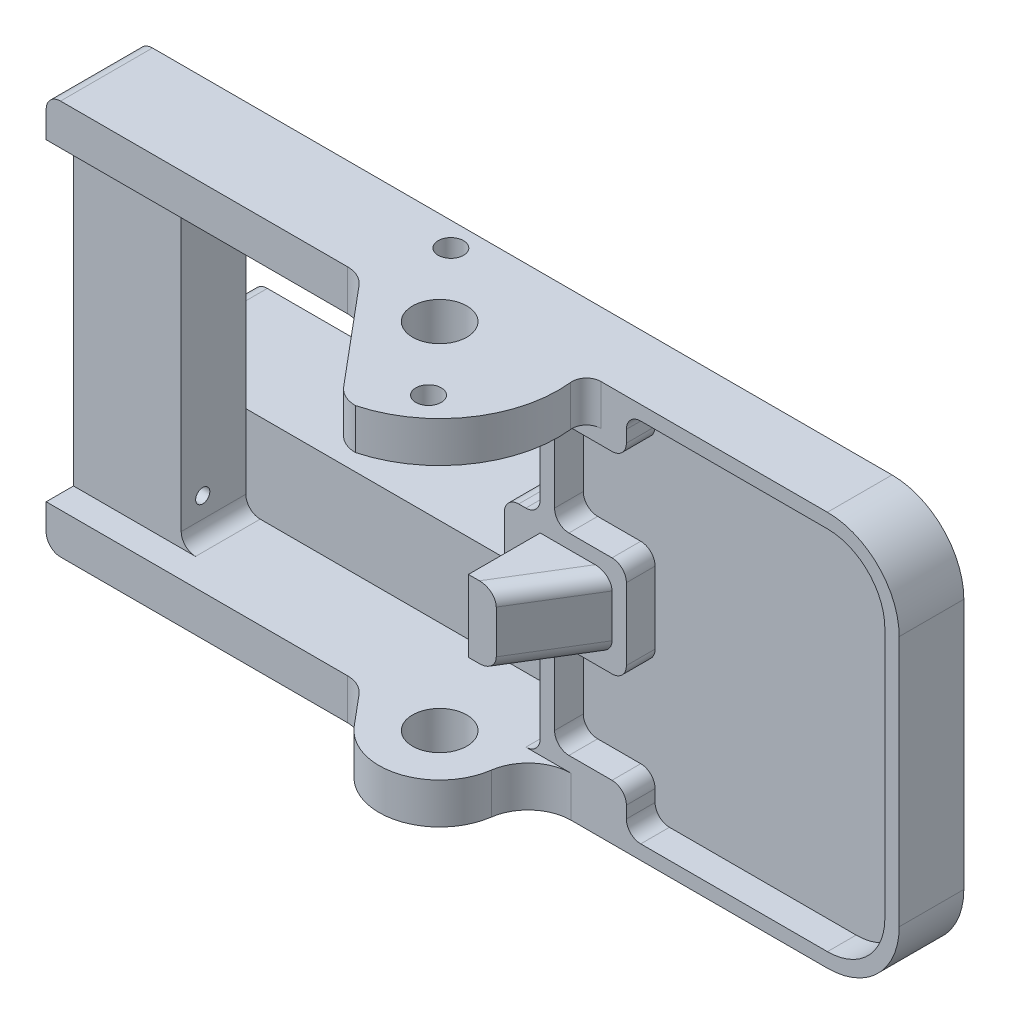
SolidWorks part; units mm, degrees
ref_plane "Front Plane" through (0, 0, 0) normal (0, 0, 1) x (1, 0, 0)
ref_plane "Top Plane" through (0, 0, 0) normal (0, 1, 0) x (1, 0, 0)
ref_plane "Right Plane" through (0, 0, 0) normal (1, 0, 0) x (0, 0, -1)
sketch "Sketch1" plane through (0, 0, 0) normal (0, 0, 1) x (1, 0, 0)
  line L1 (57.15, -34.925) -> (-57.15, -34.925)
  line L2 (57.15, -34.925) -> (57.15, 34.925)
  line L3 (57.15, 34.925) -> (-57.15, 34.925)
  line L4 (-57.15, -34.925) -> (-57.15, 34.925)
  line L5 (57.15, -34.925) -> (-57.15, 34.925) construction
  line L6 (57.15, 34.925) -> (-57.15, -34.925) construction
  point P0 (0, 0)
  dimension "D1" = 69.85
  dimension "D2" = 114.3
extrude "Boss-Extrude1" add sketch "Sketch1" along normal blind 57.15
sketch "Sketch2" plane through (0, 0, 57.15) normal (0, 0, 1) x (1, 0, 0)
  line L0 (-57.15, 34.925) -> (-57.15, -34.925) construction
  line L1 (57.15, -27.725) -> (-57.15, -27.725)
  line L2 (57.15, -27.725) -> (57.15, 27.725)
  line L3 (57.15, 27.725) -> (-57.15, 27.725)
  line L4 (-57.15, -27.725) -> (-57.15, 27.725)
  line L5 (57.15, -27.725) -> (-57.15, 27.725) construction
  line L6 (57.15, 27.725) -> (-57.15, -27.725) construction
  line L7 (57.15, 34.925) -> (-57.15, 34.925) construction
  point P0 (0, 0)
  dimension "D1" = 7.2
extrude "Cut-Extrude2" cut sketch "Sketch2" against normal blind 25.4
sketch "Sketch3" plane through (0, 0, 0) normal (0, 0, -1) x (-1, 0, 0)
  line L0 (-57.15, -34.925) -> (-57.15, 34.925) construction
  line L1 (57.15, 34.925) -> (-57.15, 34.925)
  line L2 (57.15, 34.925) -> (57.15, -12.065)
  line L3 (57.15, -12.065) -> (-57.15, -12.065)
  line L4 (-57.15, 34.925) -> (-57.15, -12.065)
  dimension "D1" = 46.99
extrude "Cut-Extrude3" cut sketch "Sketch3" against normal blind 20.32
sketch "Sketch5" plane through (0, -34.925, 0) normal (0, -1, 0) x (1, 0, 0)
  line L0 (-3.81, 10.79) -> (46.99, 10.79) construction
  line L1 (57.15, 20.32) -> (-57.15, 20.32) construction
  line L2 (57.15, 57.15) -> (57.15, 0) construction
  circle A0 centre (-3.81, 10.79) radius 2.415
  circle A1 centre (46.99, 10.79) radius 2.415
  dimension "D3" = 4.83
  dimension "D4" = 10.16
  dimension "D1" = 9.53
  dimension "D2" = 50.8
extrude "Cut-Extrude4" cut sketch "Sketch5" against normal blind 25.4
sketch "Sketch6" plane through (0, 0, 20.32) normal (0, 0, -1) x (-1, 0, 0)
  line L0 (-49.405, -12.065) -> (6.225, -12.065) construction
  line L1 (-49.405, -12.065) -> (-49.405, -34.925) construction
  line L2 (6.225, -34.925) -> (6.225, -12.065) construction
  line L3 (-57.15, -12.065) -> (57.15, -12.065) construction
  circle A1 centre (-5.08, -1.524) radius 2.2225
  dimension "D3" = 4.445
extrude "Cut-Extrude5" cut sketch "Sketch6" against normal blind 5.08
sketch "Sketch7" plane through (0, -34.925, 0) normal (0, -1, 0) x (1, 0, 0)
  line L0 (57.15, 57.15) -> (57.15, 0) construction
  line L2 (-57.15, 31.75) -> (57.15, 31.75) construction
  circle A0 centre (31.75, 36.83) radius 4.8
  dimension "D1" = 9.6
  dimension "D2" = 25.4
  dimension "D3" = 5.08
extrude "Cut-Extrude6" cut sketch "Sketch7" against normal up to surface (69.85 mm away) up to face at (0, 34.925, 38.735)
sketch "Sketch8" plane through (0, 34.925, 0) normal (0, 1, 0) x (1, 0, 0)
  line L0 (21.4654, -24.5733) -> (42.0346, -49.0867) construction
  line L1 (57.15, -31.75) -> (-57.15, -31.75) construction
  circle A0 centre (31.75, -36.83) radius 16 construction
  circle A1 centre (21.4654, -24.5733) radius 2.25
  circle A2 centre (42.0346, -49.0867) radius 2.25
  dimension "D1" = 32
  dimension "D2" = 4.5
  dimension "D3" = 50
sketch "Sketch9" plane through (0, 0, 31.75) normal (0, 0, 1) x (1, 0, 0)
  line L0 (57.15, 34.925) -> (-57.15, 34.925) construction
  line L5 (57.15, 27.725) -> (-57.15, 27.725) construction
  line L6 (-19.05, 27.725) -> (44.45, 27.725)
  line L7 (-19.05, 27.725) -> (-19.05, -27.725)
  line L8 (-19.05, -27.725) -> (44.45, -27.725)
  line L9 (44.45, 27.725) -> (44.45, -27.725)
  line L10 (-57.15, -27.725) -> (57.15, -27.725) construction
  line L11 (-57.15, 27.725) -> (-57.15, -27.725) construction
  line L12 (57.15, -27.725) -> (57.15, 27.725) construction
  line L13 (-57.15, -34.925) -> (-38.1, -34.925)
  line L14 (-57.15, -34.925) -> (-57.15, 34.925)
  line L15 (-57.15, 34.925) -> (-38.1, 34.925)
  line L16 (-38.1, -34.925) -> (-38.1, 34.925)
  line L17 (-57.15, -34.925) -> (-38.1, 34.925) construction
  line L18 (-57.15, 34.925) -> (-38.1, -34.925) construction
  line L19 (-57.15, -34.925) -> (57.15, -34.925) construction
  point P5 (-47.625, 0)
  dimension "D1" = 12.7
  dimension "25in" = 38.1
  dimension "D2" = 19.05
extrude "Cut-Extrude7" cut sketch "Sketch9" against normal through all both and the other way through all
extrude "Cut-Extrude8" cut sketch "Sketch8" against normal up to next
sketch "Sketch10" [suppressed] plane through (0, 0, 29.21) normal (0, 0, 1) x (1, 0, 0)
  line L1 (-30.607, -1.778) -> (-30.607, -6.604) construction
  circle A0 centre (-33.2489, -4.191) radius 2.286
  point P5 (-30.607, -4.191)
  dimension "D1" = 4.572
sketch "Sketch11" [suppressed] plane through (0, 0, 21.59) normal (0, 0, -1) x (-1, 0, 0)
  circle A0 centre (33.2489, -4.191) radius 2.286
  dimension "D1" = 4.572
extrude "Cut-Extrude9" [suppressed] cut sketch "Sketch11" against normal blind 3.81
sketch "Sketch12" plane through (-19.05, 0, 0) normal (1, 0, 0) x (0, 0, -1)
  line L0 (-31.75, -27.725) -> (-31.75, 27.725) construction
  line L1 (-27.94, -21.59) -> (-27.94, 21.59) construction
  line L2 (-20.32, 27.725) -> (-20.32, -12.065) construction
  circle A0 centre (-27.94, -21.59) radius 1.25
  circle A1 centre (-27.94, 21.59) radius 1.25
  point P0 (-31.75, 0)
  point P8 (-27.94, 0)
  dimension "D1" = 2.5
  dimension "D2" = 7.62
  dimension "D3" = 43.18
extrude "Cut-Extrude10" cut sketch "Sketch12" against normal up to surface (19.05 mm away) up to face at (-38.1, -2.413, 33.274)
sketch "Sketch13" plane through (0, 34.925, 0) normal (0, 1, 0) x (1, 0, 0)
  line L0 (-38.1, -36.5854) -> (17.5354, -36.5854)
  line L1 (17.5354, -36.5854) -> (34.7911, -57.15)
  line L2 (57.15, -57.15) -> (-38.1, -57.15) construction
  line L3 (42.0346, -49.0867) -> (21.4654, -24.5733) construction
  line L4 (-38.1, -36.5854) -> (-38.1, -57.15)
  line L5 (-38.1, -57.15) -> (34.7911, -57.15)
  line L6 (-38.1, -20.32) -> (-38.1, -57.15) construction
extrude "Cut-Extrude12" cut sketch "Sketch13" against normal through all
sketch "Sketch14" plane through (44.45, 0, 0) normal (-1, 0, 0) x (0, 0, 1)
  line L0 (0, -27.725) -> (31.75, -27.725) construction
  line L1 (20.32, -12.065) -> (0, -12.065)
  line L2 (20.32, -12.065) -> (20.32, -27.725)
  line L3 (20.32, -27.725) -> (0, -27.725)
  line L4 (0, -12.065) -> (0, -27.725)
extrude "Boss-Extrude2" add sketch "Sketch14" along normal up to next
sketch "Sketch15" plane through (0, 0, 20.32) normal (0, 0, -1) x (-1, 0, 0)
  line L0 (22.6367, 0.762) -> (22.6367, -4.064) construction
  line L2 (17.6714, 0.8658) -> (32.5377, 0.555) construction
  line L3 (22.6367, 0.762) -> (22.6367, -4.064) construction
  line L4 (27.4632, -4.064) -> (17.5572, -4.064) construction
  line L5 (21.717, -0.889) -> (21.717, 3.937) construction
  circle A0 centre (23.967, -1.651) radius 2.25
  point P4 (22.6367, -1.651)
  dimension "D1" = 4.5
extrude "Cut-Extrude13" cut sketch "Sketch15" against normal blind 5.08
sketch "Sketch16" plane through (0, 0, 31.75) normal (0, 0, 1) x (1, 0, 0)
  line L0 (44.45, -27.725) -> (44.45, 27.725) construction
  line L1 (57.15, -6.35) -> (44.45, -6.35)
  line L2 (57.15, -6.35) -> (57.15, 6.35)
  line L3 (57.15, 6.35) -> (44.45, 6.35)
  line L4 (44.45, -6.35) -> (44.45, 6.35)
  line L5 (57.15, -6.35) -> (44.45, 6.35) construction
  line L6 (57.15, 6.35) -> (44.45, -6.35) construction
  line L7 (57.15, 6.35) -> (57.15, -6.35) construction
  line L9 (57.15, -27.725) -> (57.15, 27.725) construction
  point P0 (50.8, 0)
  point P7 (57.15, 0)
  dimension "D1" = 12.7
extrude "Boss-Extrude3" add sketch "Sketch16" along normal blind 12.7
sketch "Sketch17" plane through (0, 6.35, 0) normal (0, 1, 0) x (1, 0, 0)
  line L0 (49.375, -44.45) -> (57.15, -31.75)
  line L1 (57.15, -44.45) -> (57.15, -31.75) construction
  line L2 (57.15, -31.75) -> (44.45, -31.75) construction
  line L3 (57.15, -31.75) -> (57.15, -44.45)
  line L4 (57.15, -44.45) -> (49.375, -44.45)
  line L5 (57.15, -44.45) -> (44.45, -44.45) construction
extrude "Cut-Extrude14" cut sketch "Sketch17" against normal blind 12.7
sketch "Sketch18" plane through (57.15, 0, 0) normal (1, 0, 0) x (0, 0, -1)
  line L1 (-20.32, -34.925) -> (-31.75, -34.925)
  line L2 (-20.32, -34.925) -> (-20.32, 34.925)
  line L3 (-20.32, 34.925) -> (-31.75, 34.925)
  line L4 (-31.75, -34.925) -> (-31.75, 34.925)
  line L5 (-57.15, -34.925) -> (0, -34.925) construction
  line L7 (-31.75, 6.35) -> (-31.75, 27.725) construction
  line L8 (-20.32, 34.925) -> (-20.32, -12.065) construction
  line L9 (-57.15, 34.925) -> (-20.32, 34.925) construction
extrude "Boss-Extrude4" add sketch "Sketch18" along normal blind 50.8
fillet "Fillet2" radius 12.7 2 edges at (107.95, -34.925, 26.035) (107.95, 34.925, 26.035)
sketch "Sketch20" plane through (0, 0, 31.75) normal (0, 0, 1) x (1, 0, 0)
  line L24 (57.15, -27.725) -> (59.69, -27.725)
  line L25 (57.15, 27.725) -> (59.69, 27.725)
  line L36 (59.69, -32.385) -> (95.25, -32.385)
  line L37 (105.41, -22.225) -> (105.41, 22.225)
  line L38 (95.25, 32.385) -> (59.69, 32.385)
  line L39 (59.69, 32.385) -> (59.69, 25.185)
  line L40 (59.69, 25.185) -> (46.99, 25.185)
  line L41 (46.99, 25.185) -> (46.99, 8.89)
  line L42 (46.99, 8.89) -> (59.69, 8.89)
  line L43 (59.69, 8.89) -> (59.69, -8.89)
  line L44 (59.69, -8.89) -> (46.99, -8.89)
  line L45 (46.99, -8.89) -> (46.99, -25.185)
  line L46 (46.99, -25.185) -> (59.69, -25.185)
  line L47 (59.69, -25.185) -> (59.69, -32.385)
  line L48 (59.69, -32.385) -> (95.25, -32.385)
  line L49 (105.41, -22.225) -> (105.41, 22.225)
  line L50 (95.25, 32.385) -> (59.69, 32.385)
  line L51 (59.69, 32.385) -> (59.69, 25.185)
  line L52 (59.69, 25.185) -> (46.99, 25.185)
  line L53 (46.99, 25.185) -> (46.99, 8.89)
  line L54 (46.99, 8.89) -> (59.69, 8.89)
  line L55 (59.69, 8.89) -> (59.69, -8.89)
  line L56 (59.69, -8.89) -> (46.99, -8.89)
  line L57 (46.99, -8.89) -> (46.99, -25.185)
  line L58 (46.99, -25.185) -> (59.69, -25.185)
  line L59 (59.69, -25.185) -> (59.69, -32.385)
  arc A6 (95.25, -32.385) -> (105.41, -22.225) centre (95.25, -22.225) ccw
  arc A7 (105.41, 22.225) -> (95.25, 32.385) centre (95.25, 22.225) ccw
  arc A8 (95.25, -32.385) -> (105.41, -22.225) centre (95.25, -22.225) ccw
  arc A9 (105.41, 22.225) -> (95.25, 32.385) centre (95.25, 22.225) ccw
  dimension "D1" = 2.54
extrude "Cut-Extrude15" cut sketch "Sketch20" against normal blind 5.08 contours L49 A9 L50 L51 L52 L53 L54 L55 L56 L57 L58 L59 L48 A8 region at (78.6465, 0, 31.75)
fillet "Fillet1" radius 5.08 4 edges at (34.7911, -31.325, 57.15) (34.7911, 31.325, 57.15) (17.5354, 31.325, 36.5854) (17.5354, -31.325, 36.5854)
fillet "Fillet4" radius 2.54 2 edges at (53.2625, -6.35, 38.1) (53.2625, 6.35, 38.1)
sketch "Sketch21" plane through (0, 34.925, 0) normal (0, 1, 0) x (1, 0, 0)
  line L0 (57.15, -31.75) -> (55.1806, -31.75)
  line L1 (37.16, -57.15) -> (57.15, -57.15)
  line L2 (57.15, -57.15) -> (57.15, -31.75)
  arc A0 (37.16, -57.15) -> (52.6554, -34.5637) centre (31.75, -36.83) ccw
  arc A1 (52.6554, -34.5637) -> (55.1806, -31.75) centre (55.1806, -34.29) cw
  dimension "D1" = 2.54
extrude "Cut-Extrude16" cut sketch "Sketch21" against normal up to next
sketch "Sketch22" plane through (0, -34.925, 0) normal (0, -1, 0) x (1, 0, 0)
  line L0 (57.15, 31.75) -> (49.9252, 31.75)
  line L11 (57.15, 31.75) -> (57.15, 57.15)
  line L12 (33.2685, 55.3354) -> (19.0581, 38.4)
  line L13 (57.15, 57.15) -> (37.16, 57.15)
  line L14 (57.15, 31.75) -> (57.15, 57.15)
  line L15 (33.2685, 55.3354) -> (23.529, 43.7283)
  line L16 (57.15, 57.15) -> (37.16, 57.15)
  arc A0 (42.3785, 38.3153) -> (23.529, 43.7283) centre (31.75, 36.83) ccw
  arc A4 (42.3785, 38.3153) -> (49.9252, 31.75) centre (49.9252, 39.37) ccw
  arc A5 (37.16, 57.15) -> (33.2685, 55.3354) centre (37.16, 52.07) ccw
  arc A6 (37.16, 57.15) -> (33.2685, 55.3354) centre (37.16, 52.07) ccw
  dimension "D2" = 7.62
  dimension "D1" = 0
extrude "Cut-Extrude17" cut sketch "Sketch22" against normal up to next
fillet "Fillet3" radius 2.54 19 edges at (59.69, 32.385, 29.21) (59.69, 25.185, 29.21) (46.99, 25.185, 29.21) (46.99, 8.89, 29.21) (59.69, 8.89, 29.21) (59.69, -8.89, 29.21) (46.99, -8.89, 29.21) (46.99, -25.185, 29.21) (59.69, -25.185, 29.21) (59.69, -32.385, 29.21) (-38.1, -34.925, 18.2927) (-38.1, 34.925, 28.4527) (-38.1, -12.065, 10.16) (57.15, -12.065, 10.16) (-19.05, -27.725, 26.035) (-19.05, 27.725, 26.035) (44.45, 27.725, 26.035) (44.45, -27.725, 26.035) (57.15, -34.925, 10.16)
sketch "Sketch23" plane through (44.45, 0, 0) normal (-1, 0, 0) x (0, 0, 1)
  line L0 (20.32, -14.605) -> (20.32, 32.385) construction
  line L1 (20.32, 8.89) -> (31.75, 8.89)
  line L2 (20.32, 8.89) -> (20.32, -8.89)
  line L3 (20.32, -8.89) -> (31.75, -8.89)
  line L4 (31.75, 8.89) -> (31.75, -8.89)
  line L5 (20.32, 8.89) -> (31.75, -8.89) construction
  line L6 (20.32, -8.89) -> (31.75, 8.89) construction
  line L7 (31.75, -27.725) -> (31.75, 27.725) construction
  line L11 (31.75, 8.89) -> (26.67, 8.89) construction
  line L12 (31.75, -8.89) -> (26.67, -8.89) construction
  point P0 (26.035, 0)
extrude "Boss-Extrude5" add sketch "Sketch23" along normal blind 6.35
fillet "Fillet5" radius 2.54 4 edges at (44.45, -8.89, 26.035) (38.1, -8.89, 26.035) (38.1, 8.89, 26.035) (44.45, 8.89, 26.035)
